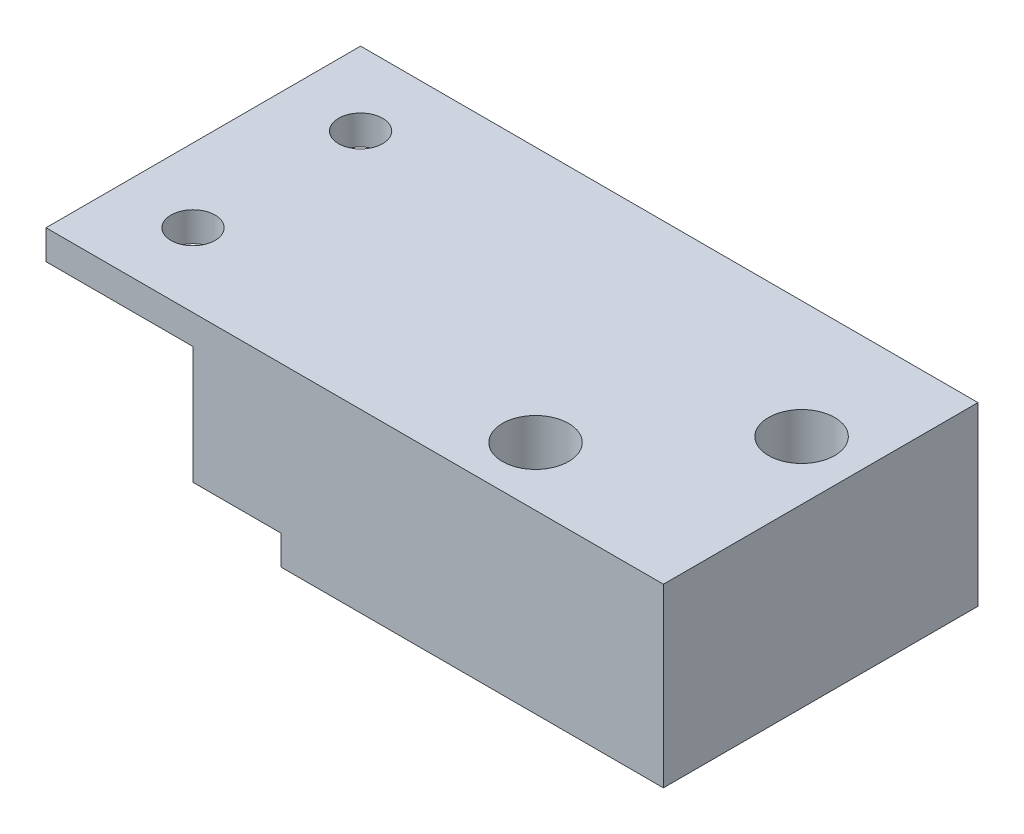
SolidWorks part; units mm, degrees
ref_plane "前视基准面" through (0, 0, 0) normal (0, 0, 1) x (1, 0, 0)
ref_plane "上视基准面" through (0, 0, 0) normal (0, 1, 0) x (1, 0, 0)
ref_plane "右视基准面" through (0, 0, 0) normal (1, 0, 0) x (0, 0, -1)
other "Configuration Table"
sketch "草图1" plane through (0, 0, 0) normal (0, 1, 0) x (1, 0, 0)
  line L33 (0, -21.4) -> (42, -21.4)
  line L34 (0, -21.4) -> (0, 0)
  line L35 (0, 0) -> (42, 0)
  line L36 (42, -21.4) -> (42, 0)
  point P0 (-90.6464, 22.0667)
  dimension "D3" = 21.4
  dimension "D6" = 42
extrude "凸台-拉伸1" add sketch "草图1" along normal blind 12 contours L33 L36 L35 L34 | L33 | L34 region at (21, 0, 10.7)
sketch "草图2" plane through (0, 0, 0) normal (0, 0, -1) x (-1, 0, 0)
  line L0 (0, 12) -> (-42, 12) construction
  line L1 (0, 0) -> (-10, 0)
  line L2 (0, 0) -> (0, 10)
  line L3 (0, 10) -> (-10, 10)
  line L4 (-10, 0) -> (-10, 10)
  line L6 (-10, 0) -> (-16, 0)
  line L7 (-10, 0) -> (-10, 2)
  line L8 (-10, 2) -> (-16, 2)
  line L9 (-16, 0) -> (-16, 2)
  dimension "D1" = 2
  dimension "D2" = 10
  dimension "D3" = 2
  dimension "D4" = 6
extrude "切除-拉伸1" cut sketch "草图2" against normal through all contours L7 L8 L9 L6 | L4 L3 L2 L1
sketch "草图3" plane through (0, 0, 0) normal (0, -1, 0) x (1, 0, 0)
  circle A0 centre (20.3, 14) radius 3.1
  dimension "D1" = 6.2
extrude "切除-拉伸2" cut sketch "草图3" against normal blind 2.6 contours A0
sketch "草图4" plane through (0, 12, 0) normal (0, 1, 0) x (1, 0, 0)
  circle A0 centre (5, -5) radius 2.25
  circle A1 centre (5, -16.4) radius 2.25
  circle A2 centre (29.3, -17.4) radius 2.25
  circle A3 centre (38, -8) radius 2.25
  circle A4 centre (5, -5) radius 1.5
  circle A5 centre (5, -16.4) radius 1.5
  circle A6 centre (38, -8) radius 1.5
  circle A7 centre (29.3, -17.4) radius 1.5
  point P12 (3.6659, -5.2968)
  point P13 (3.6659, -13.5924)
  point P14 (36.4389, -5.2968)
  point P15 (36.4389, -14.719)
  point P16 (5, -16.4)
  point P18 (5, -4.7412)
  point P19 (7.7911, -4.5907)
  point P20 (0, 0)
  point P21 (29.3, -17.4)
  point P22 (0, 0)
  point P24 (38, -8)
  point P26 (0, 0)
  dimension "D1" = 3
  dimension "D2" = 4.5
extrude "切除-拉伸3" cut sketch "草图4" against normal offset from surface (10 mm away) 2 contours A3 | A2 up to face at (20.3, 0, 10.9)
extrude "切除-拉伸4" cut sketch "草图4<3>" against normal through all contours A4 | A5 | A7 | A6
sketch "草图4<3>" plane through (0, 12, 0) normal (0, 1, 0) x (1, 0, 0) same geometry as "草图4"
